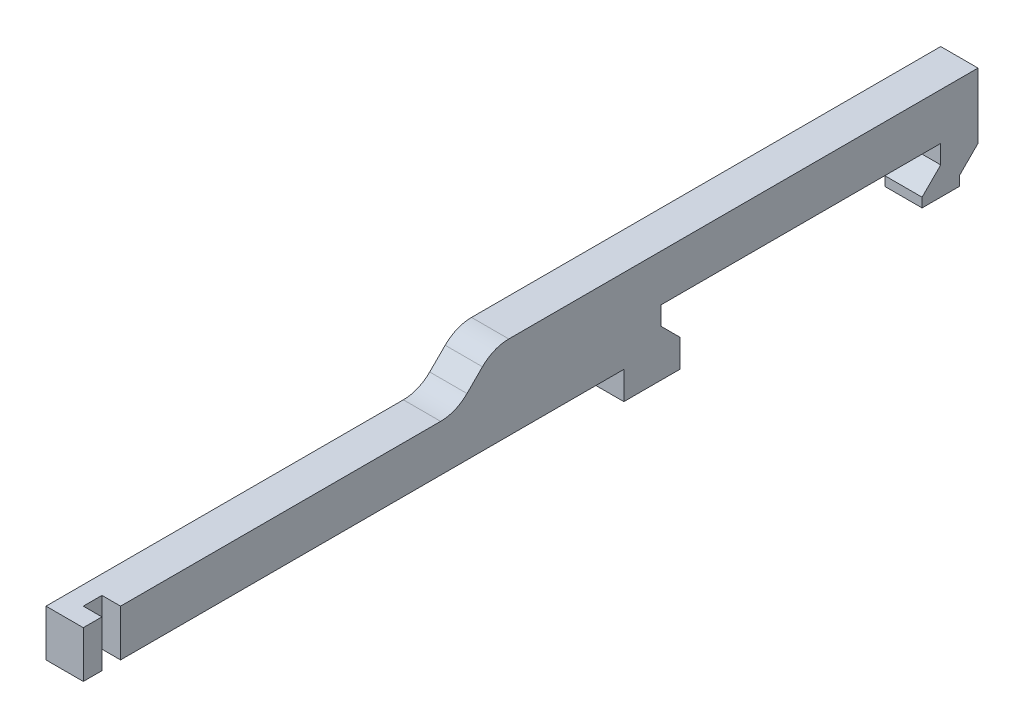
SolidWorks part; units mm, degrees
ref_plane "Спереди" through (0, 0, 0) normal (0, 0, 1) x (1, 0, 0)
ref_plane "Сверху" through (0, 0, 0) normal (0, 1, 0) x (1, 0, 0)
ref_plane "Справа" through (0, 0, 0) normal (1, 0, 0) x (0, 0, -1)
sketch "Эскиз1" plane through (0, 0, 0) normal (1, 0, 0) x (0, 0, -1)
  line L0 (20, 2.5) -> (22, 4.5)
  line L1 (0, 0) -> (20, 0)
  line L2 (0, 0) -> (0, 2.5)
  line L3 (0, 2.5) -> (20, 2.5)
  line L4 (20, 0) -> (20, 2.5)
  line L5 (22, 4.5) -> (22, 2.5) construction
  line L6 (22, 2.5) -> (20, 2.5) construction
  line L7 (22, 4.5) -> (29, 4.5)
  line L8 (20, 0) -> (29, 0)
  line L9 (29, 0) -> (29, -1.5)
  line L10 (29, -1.5) -> (32, -1.5)
  line L11 (32, -1.5) -> (32, 0)
  line L12 (32, 0) -> (31, 1)
  line L13 (31, 1) -> (31, 2)
  line L14 (31, 2) -> (46, 2)
  line L15 (32, 0) -> (31, 0) construction
  line L16 (31, 0) -> (31, 1) construction
  line L17 (38.5, 2) -> (38.5, 1) construction
  line L18 (45, 0) -> (46, 1)
  line L19 (46, 1) -> (46, 2)
  line L20 (45, 0) -> (45, -0.5)
  line L21 (45, -0.5) -> (47, -0.5)
  line L22 (47, -0.5) -> (47, 0)
  line L23 (47, 0) -> (48, 1)
  line L24 (48, 1) -> (48, 4.5)
  line L25 (48, 4.5) -> (29, 4.5)
  dimension "D1" = 2.5
  dimension "D2" = 20
  dimension "D3" = 2
  dimension "D4" = 2
  dimension "D5" = 7
  dimension "D6" = 9
  dimension "D7" = 1.5
  dimension "D8" = 3
  dimension "D9" = 1.5
  dimension "D10" = 1
  dimension "D11" = 1
  dimension "D12" = 1
  dimension "D13" = 15
  dimension "D14" = 0.5
  dimension "D15" = 2
extrude "Бобышка-Вытянуть1" add sketch "Эскиз1" along normal blind 2 contours L24 L25 L7 L0 L4 L8 L9 L10 L11 L12 L13 L14 L19 L18 L20 L21 L22 L23 | L1 L4 L3 L2 region at (0, 1.25, -10) region at (0, 2.4238, -32.8558)
fillet "Скругление1" radius 2 2 edges at (1, 4.5, -22) (1, 2.5, -20)
sketch "Эскиз2" plane through (0, 2.5, 0) normal (0, 1, 0) x (1, 0, 0)
  line L0 (2, 0) -> (2, 1) construction
  line L1 (2, 0) -> (2, 19.1716) construction
  line L3 (2, 1) -> (1, 1)
  line L4 (2, 1) -> (2, 2)
  line L5 (2, 2) -> (1, 2)
  line L6 (1, 1) -> (1, 2)
  dimension "D1" = 1
  dimension "D2" = 1
  dimension "D3" = 1
extrude "Вырез-Вытянуть1" cut sketch "Эскиз2" against normal through all
